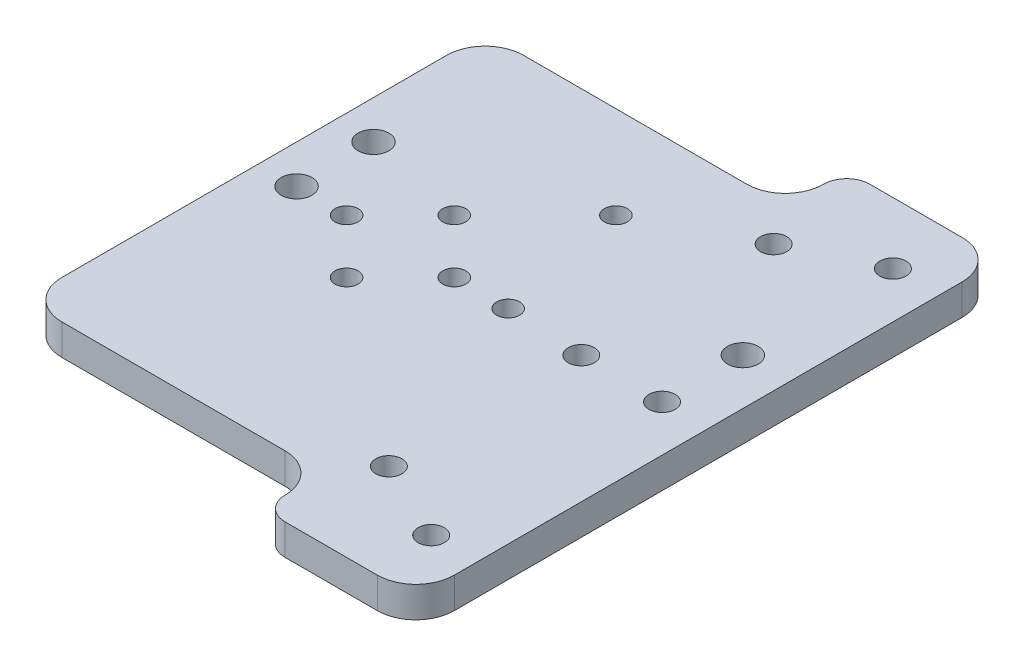
SolidWorks part; units mm, degrees
ref_plane "前视基准面" through (0, 0, 0) normal (0, 0, 1) x (1, 0, 0)
ref_plane "上视基准面" through (0, 0, 0) normal (0, 1, 0) x (1, 0, 0)
ref_plane "右视基准面" through (0, 0, 0) normal (1, 0, 0) x (0, 0, -1)
sketch "草图1" plane through (0, 0, 0) normal (0, 1, 0) x (1, 0, 0)
  line L0 (42.5, 25) -> (42.5, -25) construction
  line L5 (0, 0) -> (0, 30)
  line L6 (0, 30) -> (39, 30)
  line L7 (42.5, 0) -> (0, 0) construction
  line L8 (0, 0) -> (53, 0) construction
  line L9 (53, 30) -> (53, -30) construction
  line L10 (39, 30) -> (39, 38)
  line L11 (39, 38) -> (59, 38)
  line L12 (59, 38) -> (59, -38)
  line L13 (59, -38) -> (39, -38)
  line L14 (39, -38) -> (39, -30)
  line L15 (39, -30) -> (0, -30)
  line L16 (0, -30) -> (0, 0)
  circle A0 centre (42.5, 25) radius 1.7
  circle A1 centre (42.5, -25) radius 1.7
  circle A2 centre (42.5, 0) radius 1.7
  circle A3 centre (53, 30) radius 1.7
  circle A4 centre (53, 0) radius 1.7
  circle A5 centre (53, -30) radius 1.7
  point P0 (0, 0)
  dimension "D2" = 3.4
  dimension "D1" = 50
  dimension "D3" = 10.5
  dimension "D4" = 6
  dimension "D5" = 8
  dimension "D6" = 60
  dimension "D7" = 42.5
  dimension "D8" = 20
  dimension "D9" = 39
  dimension "D10" = 60
extrude "凸台-拉伸1" add sketch "草图1" along normal blind 4
sketch "草图2" plane through (0, 4, 0) normal (0, 1, 0) x (1, 0, 0)
  line L0 (29, 18) -> (29, 4) construction
  circle A1 centre (29, 4) radius 1.5
  circle A2 centre (29, 4) radius 1.5
  circle A3 centre (32.5, 0.5) radius 1.5
  circle A4 centre (32.5, 0.5) radius 1.5
  circle A5 centre (39.5, 7.5) radius 1.5
  circle A6 centre (39.5, 7.5) radius 1.5
  circle A7 centre (39.5, -6.5) radius 1.5
  circle A8 centre (39.5, -6.5) radius 1.5
  circle A9 centre (46.5, 0.5) radius 1.5
  circle A10 centre (46.5, 0.5) radius 1.5
  circle A11 centre (5, 0.5) radius 2
  circle A13 centre (5, 10.5) radius 2
  circle A15 centre (53, 10.5) radius 2
  circle A16 centre (53, 10.5) radius 2
  circle A17 centre (53, 0.5) radius 2
  circle A18 centre (53, 0.5) radius 2
  circle A19 centre (29, 18) radius 1.5
  circle A20 centre (29, 18) radius 1.5
  circle A21 centre (36, 11) radius 1.5
  circle A22 centre (36, 11) radius 1.5
  circle A23 centre (18.5, -6.5) radius 1.5
  circle A24 centre (11.5, 0.5) radius 1.5
  circle A25 centre (25.5, 0.5) radius 1.5
  circle A28 centre (18.5, 7.5) radius 1.5
  dimension "D1" = 0
  dimension "D2" = 0
  dimension "D3" = 0
  dimension "D4" = 0
  dimension "D5" = 0
  dimension "D8" = 0
  dimension "D9" = 0
  dimension "D10" = 0
  dimension "D11" = 0
extrude "切除-拉伸1" cut sketch "草图2" against normal through all contours A13 | A11 | A24 | A28 | A23 | A25 | A20 | A4 | A16 region at (32.5, 4, -0.5) region at (5, 4, -0.5) region at (5, 4, -10.5) region at (53, 4, -10.5) region at (29, 4, -18) region at (18.5, 4, 6.5) region at (11.5, 4, -0.5) region at (25.5, 4, -0.5) region at (18.5, 4, -7.5)
fillet "圆角1" radius 5 6 edges at (0, 2, 30) (0, 2, -30) (39, 2, -30) (39, 2, 30) (59, 2, 38) (59, 2, -38)
fillet "圆角2" radius 3 2 edges at (39, 2, 38) (39, 2, -38)
